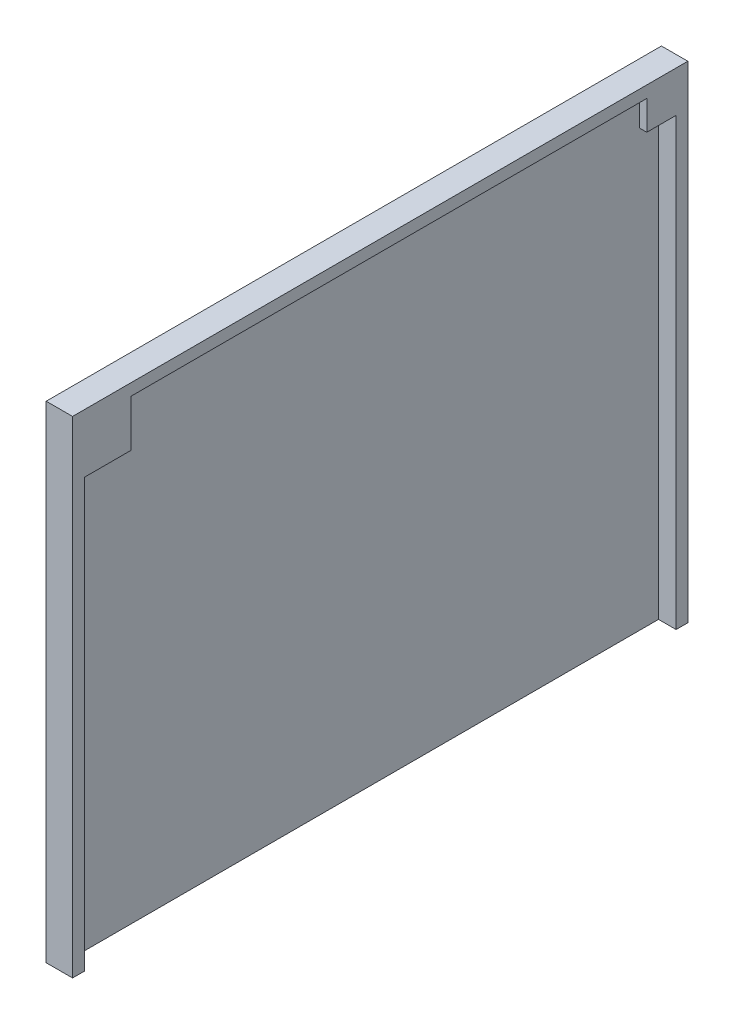
SolidWorks part; units mm, degrees
ref_plane "Front Plane" through (0, 0, 0) normal (0, 0, 1) x (1, 0, 0)
ref_plane "Top Plane" through (0, 0, 0) normal (0, 1, 0) x (1, 0, 0)
ref_plane "Right Plane" through (0, 0, 0) normal (1, 0, 0) x (0, 0, -1)
sketch "Sketch6" plane through (0, 0, 0) normal (1, 0, 0) x (0, 0, -1)
  line L1 (0, 0) -> (105, 0)
  line L2 (0, 0) -> (0, -83)
  line L3 (0, -83) -> (105, -83)
  line L4 (105, 0) -> (105, -83)
  dimension "D1" = 105
  dimension "D2" = 83
extrude "Boss-Extrude3" add sketch "Sketch6" along normal blind 4.5
sketch "Sketch9" plane through (0, -83, 0) normal (0, -1, 0) x (1, 0, 0)
  line L0 (4.5, 0) -> (4.5, -105) construction
  line L1 (0, 0) -> (0, -105) construction
  line L2 (4.5, -2) -> (1.5, -2)
  line L3 (4.5, -2) -> (4.5, -103)
  line L4 (4.5, -103) -> (1.5, -103)
  line L5 (1.5, -2) -> (1.5, -103)
  line L6 (4.5, 0) -> (0, 0) construction
  line L7 (4.5, -105) -> (0, -105) construction
  dimension "D1" = 1.5
  dimension "D2" = 2
  dimension "D3" = 2
extrude "Cut-Extrude6" cut sketch "Sketch9" against normal blind 81
sketch "Sketch10" plane through (0, 0, -2) normal (0, 0, -1) x (-1, 0, 0)
  line L1 (-4.5, -2) -> (-3.5, -2)
  line L2 (-4.5, -2) -> (-4.5, -10)
  line L3 (-4.5, -10) -> (-3.5, -10)
  line L4 (-3.5, -2) -> (-3.5, -10)
  dimension "D1" = 1
  dimension "D2" = 8
extrude "Boss-Extrude4" add sketch "Sketch10" along normal blind 8
sketch "Sketch11" plane through (0, 0, -103) normal (0, 0, 1) x (1, 0, 0)
  line L1 (4.5, -2) -> (3.2738, -2)
  line L2 (4.5, -2) -> (4.5, -7)
  line L3 (4.5, -7) -> (3.2738, -7)
  line L4 (3.2738, -2) -> (3.2738, -7)
  dimension "D1" = 5
extrude "Boss-Extrude5" add sketch "Sketch11" along normal blind 5
